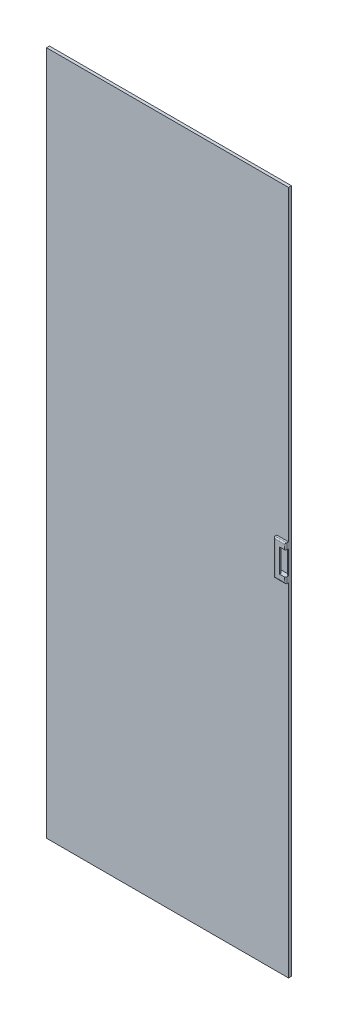
SolidWorks part; units mm, degrees
ref_plane "Front Plane" through (0, 0, 0) normal (0, 0, 1) x (1, 0, 0)
ref_plane "Top Plane" through (0, 0, 0) normal (0, 1, 0) x (1, 0, 0)
ref_plane "Right Plane" through (0, 0, 0) normal (1, 0, 0) x (0, 0, -1)
sketch "Sketch1" plane through (0, 0, 0) normal (0, 0, 1) x (1, 0, 0)
  line L1 (-260.35, 736.6) -> (260.35, 736.6)
  line L2 (-260.35, 736.6) -> (-260.35, -736.6)
  line L3 (-260.35, -736.6) -> (260.35, -736.6)
  line L4 (260.35, 736.6) -> (260.35, -736.6)
  line L5 (-260.35, 736.6) -> (260.35, -736.6) construction
  line L6 (-260.35, -736.6) -> (260.35, 736.6) construction
  point P0 (0, 0)
  dimension "D1" = 520.7
  dimension "D2" = 1473.2
extrude "Boss-Extrude1" add sketch "Sketch1" along normal blind 6.35
sketch "Sketch2" plane through (0, 0, 6.35) normal (0, 0, 1) x (1, 0, 0)
  line L1 (260.35, 0) -> (234.95, 0)
  line L2 (260.35, 76.2) -> (234.95, 76.2)
  line L3 (234.95, 0) -> (234.95, 76.2)
  line L4 (260.35, -736.6) -> (260.35, 736.6) construction
  line L5 (260.35, 76.2) -> (260.35, 63.4381)
  line L6 (260.35, 63.4381) -> (260.35, 12.6205)
  line L7 (260.35, 12.6205) -> (260.35, 0)
  line L9 (260.35, 63.4381) -> (247.65, 63.4381)
  line L10 (260.35, 63.4381) -> (260.35, 12.6205)
  line L11 (260.35, 12.6205) -> (247.65, 12.6205)
  line L12 (247.65, 63.4381) -> (247.65, 12.6205)
  line L13 (260.35, 63.4381) -> (257.7264, 63.4381)
  line L14 (260.35, 63.4381) -> (260.35, 12.6205)
  line L15 (260.35, 12.6205) -> (257.7264, 12.6205)
  line L16 (257.7264, 63.4381) -> (257.7264, 12.6205)
  line M1 (260.35, -736.6) -> (260.35, 736.6)
  dimension "D1" = 76.2
  dimension "D2" = 12.7
  dimension "D3" = 25.4
  dimension "D4" = 25.4
extrude "Boss-Extrude2" add sketch "Sketch2" along normal blind 6.35 contours L12 L9 L2 L3 L1 L11 M1 region at (244.4733, 38.1354, 6.35)
extrude "Cut-Extrude1" cut sketch "Sketch2<4>" against normal blind 3.175 contours L16 L9 L12 L11 region at (252.6882, 38.0293, 6.35)
sketch "Sketch2<4>" plane through (0, 0, 6.35) normal (0, 0, 1) x (1, 0, 0) same geometry as "Sketch2"
sketch "Sketch4" plane through (247.65, 0, 0) normal (1, 0, 0) x (0, 0, -1)
  line L0 (-12.7, 12.6205) -> (-3.175, 12.6205) construction
  line L1 (-3.175, 63.4381) -> (-7.9375, 63.4381)
  line L2 (-3.175, 63.4381) -> (-3.175, 12.6205)
  line L3 (-3.175, 12.6205) -> (-7.9375, 12.6205)
  line L4 (-7.9375, 63.4381) -> (-7.9375, 12.6205)
extrude "Cut-Extrude2" cut sketch "Sketch4" against normal blind 6.35
fillet "Fillet1" radius 2.54 1 edges at (247.65, 38.0293, 7.9375)
fillet "Fillet2" radius 2.54 5 edges at (260.35, 69.8191, 12.7) (260.35, 6.3102, 12.7) (247.65, 0, 12.7) (247.65, 76.2, 12.7) (234.95, 38.1, 12.7)
